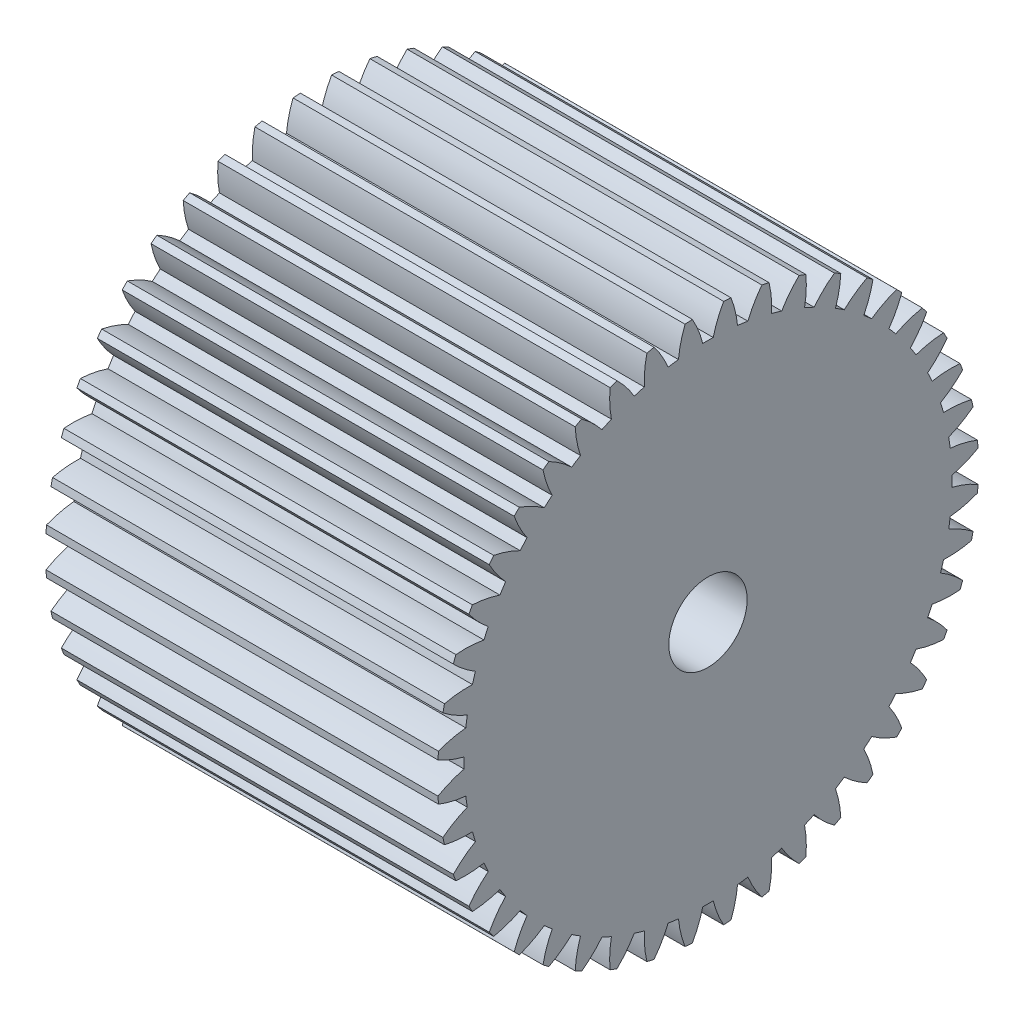
SolidWorks part; units mm, degrees
ref_plane "Plane1" through (0, 0, 0) normal (0, 0, 1) x (1, 0, 0)
ref_plane "Plane2" through (0, 0, 0) normal (0, 1, 0) x (1, 0, 0)
ref_plane "Plane3" through (0, 0, 0) normal (1, 0, 0) x (0, 0, -1)
sketch "HoldingSke" plane through (0, 0, 0) normal (0, 1, 0) x (1, 0, 0)
  line L0 (0, 0) -> (1.1989, -1.1578)
  line L1 (-15, 0) -> (100, 0) construction
  line L2 (0, 0) -> (-2.1039, 2.3779)
  line L3 (0, 0) -> (-11.863, 4.5341)
  line L4 (0, 0) -> (6.2122, 5.9991)
  line L5 (0, 0) -> (-46.8476, -17.4728)
  line L6 (0, 0) -> (-16.5793, -11.1861)
  line L7 (-2.1039, 2.3779) -> (8.6586, 51.2059)
  line L8 (-76.2, 54.61) -> (-75.5, 54.61)
  line L9 (-71.009, 38.7566) -> (-53.1078, 45.2721)
  line L10 (-76.2, 71.12) -> (104.1128, 71.12)
  line L11 (0, 0) -> (-20, 0)
  line L12 (-76.2, 101.6) -> (-76.177, 101.6)
  line L13 (24.9733, 27.94) -> (52.9518, 28.4284)
  line L14 (24.9733, 27.94) -> (24.9743, 27.94)
  line L15 (24.9733, 27.94) -> (100.4006, 29.5858)
  line L16 (-63.627, -0.6) -> (-12.827, -0.6)
  circle A0 centre (0, 0) radius 2
  circle A1 centre (0, 0) radius 12.449
  circle A2 centre (0, 0) radius 37.5
  circle A3 centre (0, 0) radius 2
  dimension "Num_teeth" = 44
  dimension "Pitch_radius" = 180.3128
  dimension "Width" = 20
  dimension "Thickness" = 20
sketch "BasProSke" plane through (0, 0, 0) normal (0, 1, 0) x (1, 0, 0)
  line L0 (-10, 0) -> (60, 0) construction
  line L1 (0, 0) -> (0, 13.8)
  line L2 (0, 0) -> (20, 0)
  line L3 (20, 0) -> (20, 13.8)
  line L4 (20, 13.8) -> (0, 13.8)
  dimension "Diameter" = 27.6
revolve "Base-Revolve" add sketch "BasProSke" angle 360 about L0
sketch "TooCutSke" plane through (0, 0, 0) normal (1, 0, 0) x (0, 0, -1)
  line L1 (0, 0) -> (0, 107) construction
  line L2 (0, 0) -> (-0.5114, 13.1901) construction
  line L3 (0, 0) -> (-1.8824, 26.3187) construction
  line L4 (-0.5114, 13.1901) -> (-0.9412, 13.1594) construction
  arc A0 (0.2665, 12.4461) -> (-0.2665, 12.4461) centre (0, 0) ccw
  arc A1 (0.8119, 13.8015) -> (-0.8119, 13.8015) centre (0, 0) ccw
  circle A2 centre (0, 0) radius 13.2 construction
  circle A3 centre (0, 0) radius 12.4039 construction
  arc A4 (-0.2665, 12.4461) -> (-0.8119, 13.8015) centre (-5.3903, 11.1715) ccw
  arc A5 (0.8119, 13.8015) -> (0.2665, 12.4461) centre (5.3903, 11.1715) ccw
extrude "ToothCut" cut sketch "TooCutSke" along normal through all
fillet "Breaks" [suppressed] radius 0.012 tangent propagation no
fillet "RootFillets" [suppressed] radius 0.151
pattern_circular "TeethCuts" count 44 every 8.182 about axis through (-10, 0, 0) along (1, 0, 0) of "ToothCut", "RootFillets", "Breaks"
sketch "HubNeaOneSke" plane through (0, 0, 0) normal (-1, 0, 0) x (0, 0, 1)
  circle A0 centre (0, 0) radius 12.449
  dimension "Diameter" = 24.898
extrude "HubNearOne" [suppressed] add sketch "HubNeaOneSke" along normal blind 30.0001
sketch "HubNeaBotSke" plane through (0, 0, 0) normal (-1, 0, 0) x (0, 0, 1)
  circle A0 centre (0, 0) radius 12.449
  dimension "Diameter" = 24.898
extrude "HubNearBoth" [suppressed] add sketch "HubNeaBotSke" along normal blind 15
ref_plane "FarPln" through (20, 0, 0) normal (1, 0, 0) x (0, 0, -1)
sketch "HubFarSke" plane through (20, 0, 0) normal (1, 0, 0) x (0, 0, -1)
  circle A0 centre (0, 0) radius 12.449
  dimension "Diameter" = 24.898
extrude "HubFar" [suppressed] add sketch "HubFarSke" along normal blind 15
sketch "BorSke" plane through (0, 0, 0) normal (1, 0, 0) x (0, 0, -1)
  circle A0 centre (0, 0) radius 2
  dimension "Diameter" = 4
extrude "Bore" cut sketch "BorSke" along normal mid plane 100.0001
sketch "KeySke" plane through (0, 0, 0) normal (1, 0, 0) x (0, 0, -1)
  line L0 (-0.8, 0) -> (-0.8, 2.7)
  line L1 (-0.8, 2.7) -> (0.8, 2.7)
  line L2 (0.8, 2.7) -> (0.8, 0)
  line L3 (0, 0) -> (0, 34) construction
  line L4 (-0.8, 0) -> (0.8, 0)
  dimension "Width" = 1.6
extrude "Keyway" [suppressed] cut sketch "KeySke" along normal mid plane 100.0001
pattern_circular "Keyway2" [suppressed] count 2 every 90 about axis through (-10, 0, 0) along (1, 0, 0) reverse direction yes
equation "' \"Module@HoldingSke\" = 6.35"
equation "' \"Num_teeth@HoldingSke\" = 12"
equation "' \"Ap@HoldingSke\" =  20"
equation "' \"Ap@HoldingSke\" = 20"
equation "' \"Width@HoldingSke\" = 0.5 * 25.4"
equation "' \"Hub_dia@HoldingSke\"= 1 * 25.4"
equation "' \"Hub_dia@HoldingSke\" = 1 * 25.4"
equation "' \"Overall_len@HoldingSke\" = 1.0 * 25.4"
equation "' \"Bore@HoldingSke\" = 0.75 * 25.4"
equation "' \"T_dim@HoldingSke\" = 0.1 * 25.4"
equation "' \"Width@KeySke\" = 0.25 * 25.4"
equation "' \"Show_teeth@HoldingSke\" = 13"
equation "' \"Backlash@HoldingSke\" = 0.009 * 25.4"
equation "' \"Addendum_fac@HoldingSke\" = 1.0"
equation "' \"Dedendum_fac@HoldingSke\" = 1.25"
equation "' \"Dedendum_add@HoldingSke\" = 0.00005 * 25.4"
equation "' \"Clearance_fac@HoldingSke\" = 0.25"
equation "\"Pitch@HoldingSke\" = 1 / \"Module@HoldingSke\""
equation "\"Overcut_dia@TooCutSke\" = (\"Num_teeth@HoldingSke\" + 2 * \"Addendum_fac@HoldingSke\") / \"Pitch@HoldingSke\" + 0.002 * 25.4"
equation "\"Pitch_dia@TooCutSke\" = \"Num_teeth@HoldingSke\" / \"Pitch@HoldingSke\""
equation "\"Base_dia@TooCutSke\" = \"Num_teeth@HoldingSke\" / \"Pitch@HoldingSke\" * cos((\"Ap@HoldingSke\"  * 3.14159265 / 180))"
equation "\"Root_dia@TooCutSke\" = (\"Num_teeth@HoldingSke\" + 2) / \"Pitch@HoldingSke\" - 2 * (\"Addendum_fac@HoldingSke\" + \"Dedendum_fac@HoldingSke\") / \"Pitch@HoldingSke\" - \"Dedendum_add@HoldingSke\" * 2"
equation "\"Half_ang@TooCutSke\" = 180 / \"Num_teeth@HoldingSke\""
equation "\"Half_CT@TooCutSke\" = \"Num_teeth@HoldingSke\" / \"Pitch@HoldingSke\" * sin((3.14159265 / 2 / \"Num_teeth@HoldingSke\")) / 2 - 7 * \"Backlash@HoldingSke\" / 4"
equation "\"Flank_rad@TooCutSke\" = \"Num_teeth@HoldingSke\" / \"Pitch@HoldingSke\" / 5"
equation "\"Radius@RootFillets\" = \"Clearance_fac@HoldingSke\" / \"Pitch@HoldingSke\" + \"Dedendum_add@HoldingSke\""
equation "\"Break_rad@Breaks\" = 0.02 / \"Pitch@HoldingSke\""
equation "\"Thickness@HoldingSke\" = \"Width@HoldingSke\""
equation "\"OAL@HoldingSke\" = \"Thickness@HoldingSke\""
equation "\"MHD@HoldingSke\" = (\"Num_teeth@HoldingSke\" + 2) / \"Pitch@HoldingSke\" - 2 * (\"Addendum_fac@HoldingSke\" + \"Dedendum_fac@HoldingSke\")  / \"Pitch@HoldingSke\" - \"Dedendum_add@HoldingSke\" * 2"
equation "\"MBD@HoldingSke\" = (\"Num_teeth@HoldingSke\" + 2) / \"Pitch@HoldingSke\" - 2 * (\"Addendum_fac@HoldingSke\" + \"Dedendum_fac@HoldingSke\")  / \"Pitch@HoldingSke\" - \"Dedendum_add@HoldingSke\" * 2 - 0.002 * 25.4"
equation "\"MHD@HoldingSke\" = ((sgn( \"MHD@HoldingSke\" - \"Hub_dia@HoldingSke\" )-1)*( \"MHD@HoldingSke\" - \"Hub_dia@HoldingSke\" ))/-2+ \"Hub_dia@HoldingSke\""
equation "\"MBD@HoldingSke\" = ((sgn( \"MBD@HoldingSke\" - \"Bore@HoldingSke\" )-1)*( \"MBD@HoldingSke\" - \"Bore@HoldingSke\" ))/-2+ \"Bore@HoldingSke\""
equation "\"OAL@HoldingSke\" = ((sgn( \"OAL@HoldingSke\" - \"Overall_len@HoldingSke\" )+1)*( \"OAL@HoldingSke\" - \"Overall_len@HoldingSke\" ))/2 + \"Overall_len@HoldingSke\" + 0.000002 * 25.4"
equation "\"Num_teeth@TeethCuts\" = int( \"Show_teeth@HoldingSke\" ) + 1"
equation "\"Num_teeth@TeethCuts\" = ((sgn( \"Num_teeth@TeethCuts\" - \"Num_teeth@HoldingSke\" )-1)*( \"Num_teeth@TeethCuts\" - \"Num_teeth@HoldingSke\" ))/-2+ \"Num_teeth@HoldingSke\""
equation "\"Num_teeth@TeethCuts\" = ((sgn( \"Num_teeth@TeethCuts\" - 2.0)+1)*( \"Num_teeth@TeethCuts\" - 2.0))/2 +2.0"
equation "\"Angle@TeethCuts\" = 360.0 / \"Num_teeth@HoldingSke\""
equation "\"Diameter@BasProSke\" = (\"Num_teeth@HoldingSke\" + 2 * \"Addendum_fac@HoldingSke\") / \"Pitch@HoldingSke\""
equation "\"Thickness@BasProSke\"  = \"Thickness@HoldingSke\""
equation "' \"Fillet_rad@BasProSke\" =  \"Thickness@HoldingSke\" * 0.05"
equation "' \"Fillet_rad@BasProSke\" = \"Thickness@HoldingSke\" * 0.05"
equation "\"MHD@HoldingSke\" = ((sgn( \"MHD@HoldingSke\" - \"Root_dia@TooCutSke\" )-1)*( \"MHD@HoldingSke\" - \"Root_dia@TooCutSke\" ))/-2+ \"Root_dia@TooCutSke\""
equation "\"Diameter@HubNeaOneSke\" = \"MHD@HoldingSke\""
equation "\"Length@HubNearOne\" = \"OAL@HoldingSke\" - \"Thickness@BasProSke\""
equation "\"Diameter@HubNeaBotSke\" = \"MHD@HoldingSke\""
equation "\"Length@HubNearBoth\" = ( \"OAL@HoldingSke\" - \"Thickness@BasProSke\" ) / 2.0"
equation "\"Thickness@FarPln\" = \"Thickness@BasProSke\""
equation "\"Diameter@HubFarSke\" = \"MHD@HoldingSke\""
equation "\"Length@HubFar\" = ( \"OAL@HoldingSke\" - \"Thickness@BasProSke\" ) / 2.0"
equation "\"Diameter@BorSke\" = \"MBD@HoldingSke\""
equation "\"D1@Bore\" = \"OAL@HoldingSke\" * 2.0"
equation "\"D1@Keyway\" = \"OAL@HoldingSke\" * 2.0"
equation "\"Offset@KeySke\" = \"T_dim@HoldingSke\" + \"MBD@HoldingSke\" / 2.0"
